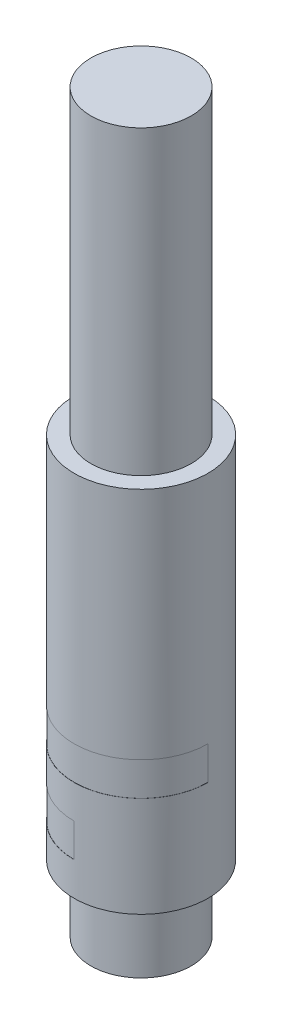
SolidWorks part; units mm, degrees
ref_plane "Front Plane" through (0, 0, 0) normal (0, 0, 1) x (1, 0, 0)
ref_plane "Top Plane" through (0, 0, 0) normal (0, 1, 0) x (1, 0, 0)
ref_plane "Right Plane" through (0, 0, 0) normal (1, 0, 0) x (0, 0, -1)
sketch "Sketch1" plane through (0, 0, 0) normal (0, 1, 0) x (1, 0, 0)
  circle A0 centre (0, 0) radius 9.525
  dimension "D1" = 19.05
extrude "Boss-Extrude1" add sketch "Sketch1" along normal blind 57.15
sketch "Sketch2" plane through (0, 0, 0) normal (0, -1, 0) x (1, 0, 0)
  circle A0 centre (0, 0) radius 12.7
  dimension "D1" = 25.4
extrude "Boss-Extrude2" add sketch "Sketch2" along normal blind 69.85
sketch "Sketch3" plane through (0, -69.85, 0) normal (0, -1, 0) x (1, 0, 0)
  circle A0 centre (0, 0) radius 9.525
  dimension "D1" = 19.05
extrude "Boss-Extrude3" add sketch "Sketch3" along normal blind 12.7
ref_plane "Plane1" through (0, -63.5, 0) normal (0, -1, 0) x (-1, 0, 0)
sketch "Sketch4" plane through (0, -63.5, 0) normal (0, -1, 0) x (-1, 0, 0)
  line L0 (0, 12.7) -> (0, 12.6746)
  line L1 (0, -12.6746) -> (0, -12.7)
  arc A0 (0, -12.7) -> (0, 12.7) centre (0, 0) ccw
  arc A1 (0, -12.6746) -> (0, 12.6746) centre (0, 0) ccw
  circle A2 centre (0, 0) radius 12.7 construction
  dimension "D1" = 0.0254
extrude "Cut-Extrude1" cut sketch "Sketch4" against normal blind 6.35
ref_plane "Plane2" through (0, -50.8, 0) normal (0, -1, 0) x (-1, 0, 0)
sketch "Sketch5" plane through (0, -50.8, 0) normal (0, -1, 0) x (1, 0, 0)
  line L0 (-12.7, 0) -> (-12.6746, 0)
  line L1 (12.6746, 0) -> (12.7, 0)
  arc A0 (12.7, 0) -> (-12.7, 0) centre (0, 0) ccw
  circle A1 centre (0, 0) radius 12.7 construction
  arc A2 (12.6746, 0) -> (-12.6746, 0) centre (0, 0) ccw
  dimension "D1" = 0.0254
extrude "Cut-Extrude2" cut sketch "Sketch5" against normal blind 6.35
